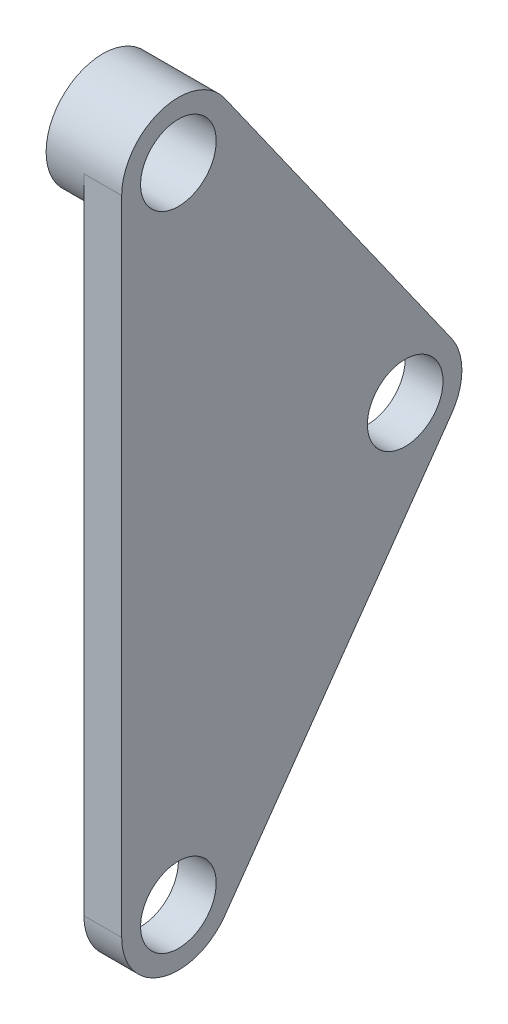
SolidWorks part; units mm, degrees
ref_plane "前视基准面" through (0, 0, 0) normal (0, 0, 1) x (1, 0, 0)
ref_plane "上视基准面" through (0, 0, 0) normal (0, 1, 0) x (1, 0, 0)
ref_plane "右视基准面" through (0, 0, 0) normal (1, 0, 0) x (0, 0, -1)
other "Configuration Table"
sketch "草图1" plane through (0, 0, 0) normal (1, 0, 0) x (0, 0, -1)
  line L0 (0, -20) -> (18, -20) construction
  line L1 (0, 0) -> (18, 0) construction
  line L2 (0, 0) -> (0, -40)
  line L3 (0, -40) -> (18, -40) construction
  line L4 (18, 0) -> (18, -40) construction
  line L5 (5.4509, -1.27) -> (17.4509, -18.27)
  line L6 (17.4509, -21.73) -> (5.4509, -38.73)
  circle A0 centre (3, -3) radius 3
  circle A1 centre (3, -37) radius 3
  circle A2 centre (15, -20) radius 3
  circle A3 centre (3, -3) radius 2
  circle A4 centre (15, -20) radius 2
  circle A5 centre (3, -37) radius 2
  dimension "D1" = 6
  dimension "D2" = 4
  dimension "D3" = 40
  dimension "D4" = 18
extrude "凸台-拉伸1" add sketch "草图1" along normal blind 2 contours A2 L5 A0 L2 A1 L6 | A0 | A2 | A1 region at (0, -20, -6.4523)
extrude "凸台-拉伸2" add sketch "草图1<4>" against normal blind 2 contours A0
sketch "草图1<4>" plane through (0, 0, 0) normal (1, 0, 0) x (0, 0, -1) same geometry as "草图1"
extrude "切除-拉伸1" cut sketch "草图1<3>" along normal through all both and the other way through all contours A3 | A4 | A5
sketch "草图1<3>" plane through (0, 0, 0) normal (1, 0, 0) x (0, 0, -1) same geometry as "草图1"
